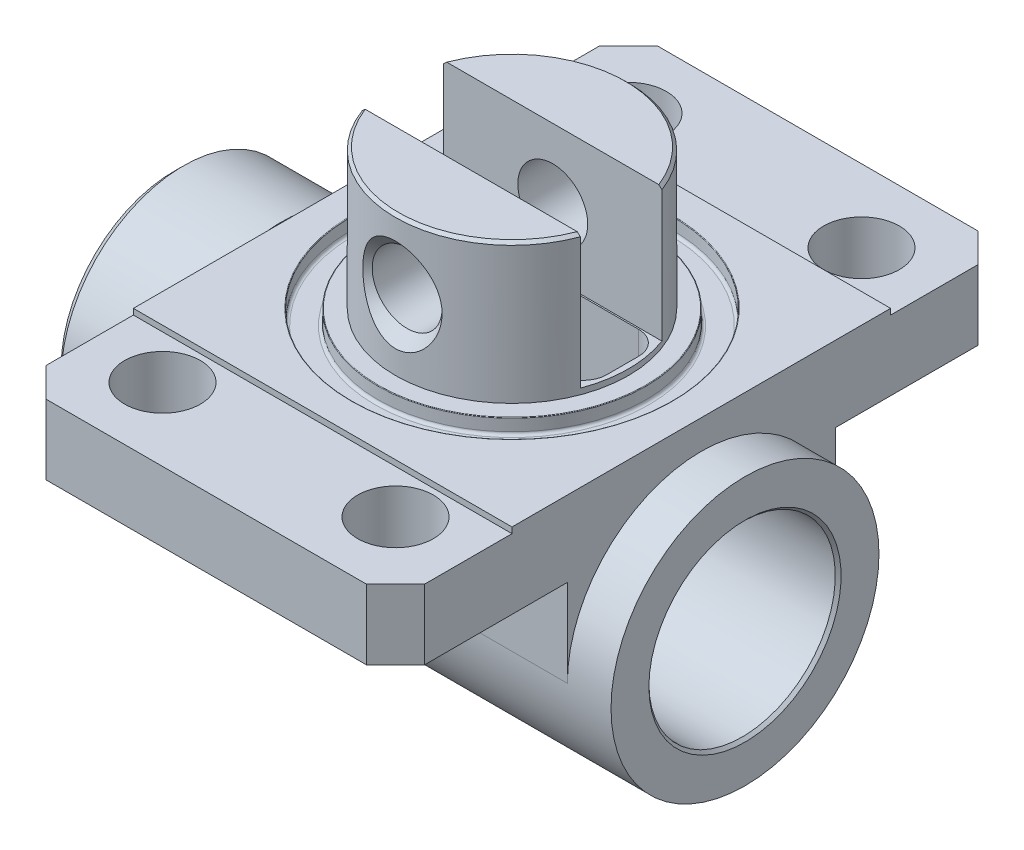
SolidWorks part; units mm, degrees
material "Простая углеродистая сталь"
ref_plane "Спереди" through (0, 0, 0) normal (0, 0, 1) x (1, 0, 0)
ref_plane "Сверху" through (0, 0, 0) normal (0, 1, 0) x (1, 0, 0)
ref_plane "Справа" through (0, 0, 0) normal (1, 0, 0) x (0, 0, -1)
sketch "Эскиз1" plane through (0, 0, 0) normal (0, 0, 1) x (1, 0, 0)
  line L0 (-81.569, -40) -> (63.5139, -40) construction
  line L1 (-58, -24) -> (39.5, -24)
  line L10 (40, -23.5) -> (40, -17)
  line L11 (40, -17) -> (-36, -17)
  line L12 (-36, -17) -> (-36, -19.35)
  line L13 (-36.8, -20.15) -> (-38.1686, -20.15)
  line L14 (-38.7343, -19.9157) -> (-39.65, -19)
  line L15 (-39.65, -19) -> (-56.4, -19)
  line L16 (-58, -20.6) -> (-58, -24)
  line L17 (-56.4, -19) -> (-58, -20.6)
  line L18 (39.5, -24) -> (40, -23.5)
  line L19 (-58, -24) -> (-58, -40)
  line L20 (-58, -40) -> (40, -40)
  line L21 (40, -40) -> (40, -23.5)
  arc A0 (-36, -19.35) -> (-36.8, -20.15) centre (-36.8, -19.35) cw
  arc A1 (-38.1686, -20.15) -> (-38.7343, -19.9157) centre (-38.1686, -19.35) cw
  point P14 (40, -24)
  point P20 (-58, -19)
  point P22 (-36, -20.15)
  point P25 (-38.5, -20.15)
  dimension "D15" = 0.8
  dimension "D1" = 40
  dimension "D2" = 16
  dimension "D3" = 42
  dimension "D4" = 46
  dimension "D5" = 22
  dimension "D6" = 45
  dimension "D9" = 58
  dimension "D10" = 98
  dimension "D12" = 45
  dimension "D13" = 39.7
  dimension "D14" = 2.5
  dimension "D16" = 1.6
  dimension "D17" = 45
  dimension "D18" = 0.5
revolve "Повернуть1" add sketch "Эскиз1" angle 360 about L0 region at (-6.1363, -20.6791, 0) region at (-8.9961, -31.9993, 0)
cosmetic thread "Условное изображение резьбы1" parameters "D2"=40.5
sketch "Эскиз2" plane through (0, 0, 0) normal (0, 0, 1) x (1, 0, 0)
  line L0 (0, 30.1132) -> (0, -50.7908) construction
  line L1 (0, 12) -> (-19.5, 12)
  line L2 (-20, 11.5) -> (-20, -40)
  line L3 (-20, -40) -> (0, -40)
  line L4 (0, -40) -> (0, 12)
  line L5 (-26.8067, -40) -> (-60.8926, -40) construction
  line L6 (-36, -63) -> (40, -63) construction
  line L7 (-19.5, 12) -> (-20, 11.5)
  point P4 (-20, 12)
  dimension "D1" = 75
  dimension "D2" = 40
  dimension "D3" = 0.5
  dimension "D4" = 45
revolve "Повернуть2" add sketch "Эскиз2" angle 360 about L0
sketch "Эскиз3" plane through (0, 12, 0) normal (0, 1, 0) x (1, 0, 0)
  line L0 (-32.5, 47.5) -> (-27.5, 52.5)
  line L1 (-27.5, -52.5) -> (27.5, -52.5)
  line L2 (-32.5, -47.5) -> (-32.5, 47.5)
  line L3 (-27.5, 52.5) -> (27.5, 52.5)
  line L4 (32.5, -47.5) -> (32.5, 47.5)
  line L5 (-32.5, -52.5) -> (32.5, 52.5) construction
  line L6 (-32.5, 52.5) -> (32.5, -52.5) construction
  line L7 (27.5, 52.5) -> (32.5, 47.5)
  line L8 (27.5, -52.5) -> (32.5, -47.5)
  line L9 (-32.5, -47.5) -> (-27.5, -52.5)
  line L10 (-32.5, 32.5) -> (32.5, 32.5)
  line L11 (32.5, -32.5) -> (-32.5, -32.5)
  line L12 (0, 32.5) -> (0, -32.5) construction
  point P0 (0, 0)
  circle M1 centre (0, 0) radius 19.5
  dimension "D1" = 105
  dimension "D2" = 65
  dimension "D3" = 5
  dimension "D4" = 45
  dimension "D5" = 5
  dimension "D6" = 45
  dimension "D7" = 5
  dimension "D8" = 45
  dimension "D9" = 5
  dimension "D10" = 45
  dimension "D11" = 65
extrude "Бобышка-Вытянуть1" add sketch "Эскиз3" against normal blind 1 from offset 24 contours L11 L4 L10 L2 M1 region at (0, 12, -31.5808) offset against normal yes
sketch "Эскиз4" plane through (0, -13, 0) normal (0, -1, 0) x (1, 0, 0)
  line L8 (-32.5, -47.5) -> (-27.5, -52.5)
  line L9 (-27.5, -52.5) -> (27.5, -52.5)
  line L10 (27.5, -52.5) -> (32.5, -47.5)
  line L11 (32.5, -47.5) -> (32.5, 47.5)
  line L12 (32.5, 47.5) -> (27.5, 52.5)
  line L13 (27.5, 52.5) -> (-27.5, 52.5)
  line L14 (-27.5, 52.5) -> (-32.5, 47.5)
  line L15 (-32.5, 47.5) -> (-32.5, -47.5)
  line L16 (-32.5, -47.5) -> (-27.5, -52.5)
  line L17 (-27.5, -52.5) -> (27.5, -52.5)
  line L18 (27.5, -52.5) -> (32.5, -47.5)
  line L19 (32.5, -47.5) -> (32.5, 47.5)
  line L20 (32.5, 47.5) -> (27.5, 52.5)
  line L21 (27.5, 52.5) -> (-27.5, 52.5)
  line L22 (-27.5, 52.5) -> (-32.5, 47.5)
  line L23 (-32.5, 47.5) -> (-32.5, -47.5)
  dimension "D1" = 0
extrude "Бобышка-Вытянуть3" add sketch "Эскиз4" along normal blind 12
sketch "Эскиз5" plane through (0, 0, 0) normal (0, 0, 1) x (1, 0, 0)
  line L0 (0, 0) -> (0, -70.6043) construction
  line L1 (32.5, -12) -> (-32.5, -12) construction
  line L2 (-23, -12) -> (-27.5, -12)
  line L3 (-23, -12) -> (-23, -14.1)
  line L4 (-23.5, -14.6) -> (-27, -14.6)
  line L5 (-27.5, -12) -> (-27.5, -14.1)
  arc A0 (-23, -14.1) -> (-23.5, -14.6) centre (-23.5, -14.1) cw
  arc A1 (-27, -14.6) -> (-27.5, -14.1) centre (-27, -14.1) cw
  point P13 (-27.5, -14.6)
  dimension "D4" = 0.5
  dimension "D1" = 46
  dimension "D2" = 55
  dimension "D3" = 2.6
revolve "Вырез-Повернуть1" cut sketch "Эскиз5" angle 360 about L0
fillet "Скругление1" radius 0.1 2 edges at (0, -12, 23) (0, -12, 27.5)
sketch "Эскиз6" plane through (0, 12, 0) normal (0, 1, 0) x (1, 0, 0)
  line L1 (-20, 7) -> (20, 7)
  line L2 (-20, 7) -> (-20, -7)
  line L3 (-20, -7) -> (20, -7)
  line L4 (20, 7) -> (20, -7)
  line L5 (-20, 7) -> (20, -7) construction
  line L6 (-20, -7) -> (20, 7) construction
  circle A1 centre (0, 0) radius 20 construction
  point P2 (0, 0)
  dimension "b" = 14
extrude "Вырез-Вытянуть1" cut sketch "Эскиз6" against normal blind 23
revolve "Вырез-Повернуть2" cut sketch "Эскиз1<3>" angle 360 about L0 region at (-8.9961, -31.9993, 0)
sketch "Эскиз1<3>" plane through (0, 0, 0) normal (0, 0, 1) x (1, 0, 0) same geometry as "Эскиз1"
sketch "Эскиз8" plane through (0, 12, 0) normal (0, 1, 0) x (1, 0, 0)
  line L1 (-15, 6.75) -> (15, 6.75)
  line L2 (-19, 2.75) -> (-19, -2.75)
  line L3 (-15, -6.75) -> (15, -6.75)
  line L4 (19, 2.75) -> (19, -2.75)
  line L5 (-19, 6.75) -> (19, -6.75) construction
  line L6 (-19, -6.75) -> (19, 6.75) construction
  arc A0 (-15, 6.75) -> (-19, 2.75) centre (-15, 2.75) ccw
  arc A1 (-19, -2.75) -> (-15, -6.75) centre (-15, -2.75) ccw
  arc A2 (15, -6.75) -> (19, -2.75) centre (15, -2.75) ccw
  arc A3 (15, 6.75) -> (19, 2.75) centre (15, 2.75) cw
  point P0 (0, 0)
  dimension "D1" = 4
  dimension "b1" = 13.5
  dimension "D3" = 38
extrude "Вырез-Вытянуть2" cut sketch "Эскиз8" against normal up to next
sketch "Эскиз9" plane through (0, 0, 0) normal (0, 0, 1) x (1, 0, 0)
  circle A0 centre (0, 0) radius 6
  dimension "d" = 12
extrude "Вырез-Вытянуть3" cut sketch "Эскиз9" against normal through all and the other way through all
sketch "Эскиз10" plane through (0, -12, 0) normal (0, 1, 0) x (1, 0, 0)
  line L1 (-20, -40) -> (20, -40) construction
  line L2 (-20, -40) -> (-20, 40) construction
  line L3 (-20, 40) -> (20, 40) construction
  line L4 (20, -40) -> (20, 40) construction
  line L5 (-20, -40) -> (20, 40) construction
  line L6 (-20, 40) -> (20, -40) construction
  circle A0 centre (-20, 40) radius 6.5
  circle A1 centre (20, 40) radius 6.5
  circle A2 centre (20, -40) radius 6.5
  circle A3 centre (-20, -40) radius 6.5
  point P0 (0, 0)
  dimension "D3" = 13
  dimension "D1" = 40
  dimension "D2" = 80
extrude "Вырез-Вытянуть4" cut sketch "Эскиз10" against normal through all
sketch "Эскиз11" plane through (32.5, 0, 0) normal (1, 0, 0) x (0, 0, -1)
  line L0 (-17.4356, -25) -> (-47.5, -25) construction
  line L1 (47.5, -25) -> (17.4356, -25) construction
  line L2 (-17.4356, -25) -> (-23, -25)
  line L3 (23, -25) -> (17.4356, -25)
  line L4 (-23, -40) -> (-23, -25)
  line L5 (23, -40) -> (23, -25)
  circle A0 centre (0, -40) radius 23 construction
  arc A1 (-17.4356, -25) -> (-23, -40) centre (0, -40) ccw
  arc A2 (23, -40) -> (17.4356, -25) centre (0, -40) ccw
extrude "Бобышка-Вытянуть4" add sketch "Эскиз11" against normal up to surface (65 mm away) up to face at (-32.5, -16.8, 0)
ref_plane "Плоскость1" through (0, 0, 18) normal (0, 0, 1) x (1, 0, 0)
sketch "Эскиз12" plane through (0, 0, 18) normal (0, 0, 1) x (1, 0, 0)
  circle A0 centre (0, 0) radius 6
  circle A2 centre (0, 0) radius 6 construction
extrude "Вырез-Вытянуть5" cut sketch "Эскиз12" along normal blind 2 draft 45 draft outward yes
mirror "Зеркальное отражение1" about plane through (0, 0, 0) normal (0, 0, 1) of "Вырез-Вытянуть5"
